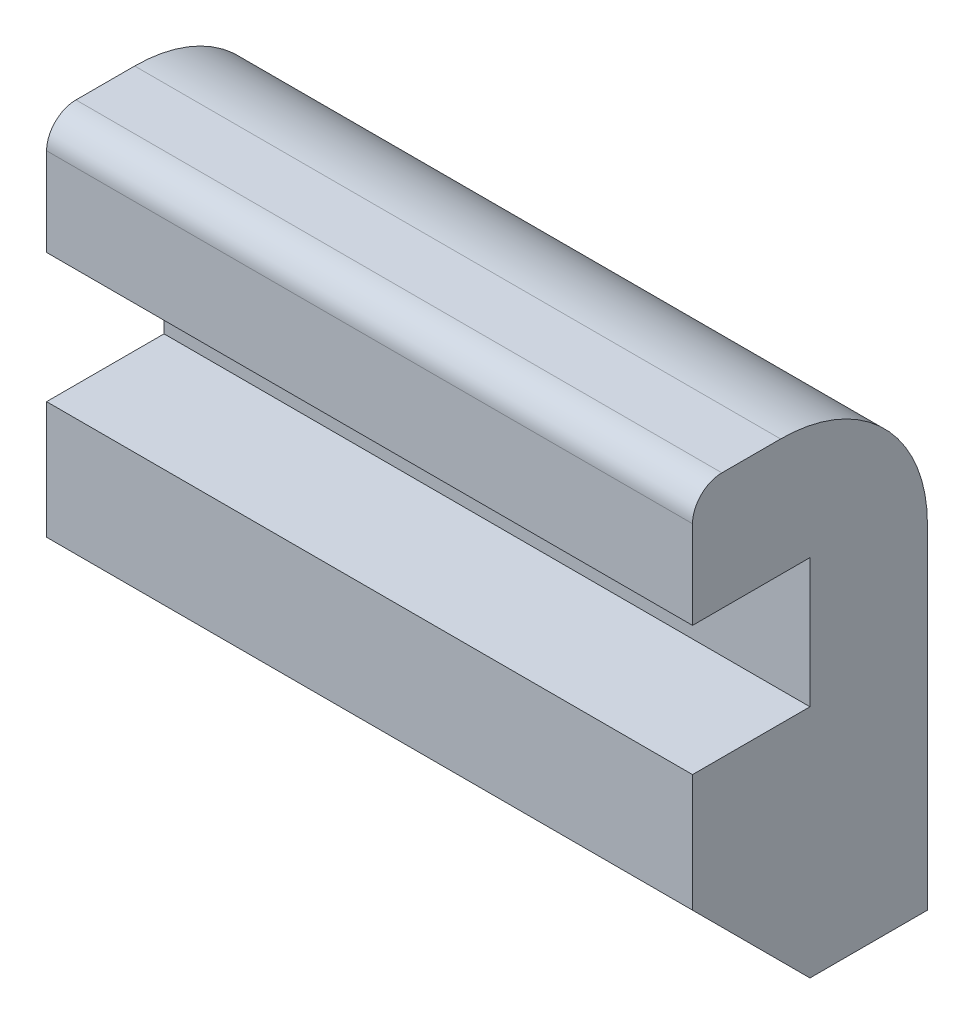
SolidWorks part; units mm, degrees
ref_plane "Front Plane" through (0, 0, 0) normal (0, 0, 1) x (1, 0, 0)
ref_plane "Top Plane" through (0, 0, 0) normal (0, 1, 0) x (1, 0, 0)
ref_plane "Right Plane" through (0, 0, 0) normal (1, 0, 0) x (0, 0, -1)
sketch "Sketch1" plane through (0, 0, 0) normal (0, 1, 0) x (1, 0, 0)
  line L1 (-19.5, 77.5) -> (19.5, 77.5)
  line L2 (-19.5, 77.5) -> (-19.5, -77.5)
  line L3 (-19.5, -77.5) -> (19.5, -77.5)
  line L4 (19.5, 77.5) -> (19.5, -77.5)
  line L5 (-19.5, 77.5) -> (19.5, -77.5) construction
  line L6 (-19.5, -77.5) -> (19.5, 77.5) construction
  point P0 (0, 0)
  dimension "D1" = 39
  dimension "D2" = 155
extrude "Boss-Extrude1" add sketch "Sketch1" along normal blind 2
sketch "Sketch2" plane through (0, 2, 0) normal (0, 1, 0) x (1, 0, 0)
  line L0 (-17.5, -75.5) -> (-17.5, -77.5)
  line L1 (-19.5, 77.5) -> (19.5, 77.5)
  line L2 (-19.5, 77.5) -> (-19.5, -77.5)
  line L3 (-19.5, -77.5) -> (19.5, -77.5)
  line L4 (19.5, 77.5) -> (19.5, -77.5)
  line L5 (-17.5, 75.5) -> (17.5, 75.5)
  line L6 (-17.5, 75.5) -> (-17.5, -75.5)
  line L7 (-17.5, -75.5) -> (17.5, -75.5)
  line L8 (17.5, 75.5) -> (17.5, -75.5)
  line L9 (-17.5, 75.5) -> (17.5, -75.5) construction
  line L10 (-17.5, -75.5) -> (17.5, 75.5) construction
  line L11 (17.5, -75.5) -> (17.5, -77.5)
  point P6 (0, 0)
  line M9 (19.5, -77.5) -> (19.5, 77.5)
  line M10 (19.5, 77.5) -> (-19.5, 77.5)
  line M11 (-19.5, 77.5) -> (-19.5, -77.5)
  line M12 (-19.5, -77.5) -> (19.5, -77.5)
  dimension "D1" = 2
  dimension "D2" = 2
extrude "Boss-Extrude2" add sketch "Sketch2" along normal blind 38 contours L8 L11 L3 L0 L6 L5 M9 M10 M11 M12 region at (-19.0983, 2, 76.5)
sketch "Sketch3" plane through (0, 2, 0) normal (0, 1, 0) x (1, 0, 0)
  line L0 (-17.5, 75.5) -> (-17.5, -77.5) construction
  line L1 (-17.5, -77.5) -> (-15.5, -77.5)
  line L2 (-17.5, -77.5) -> (-17.5, -75.5)
  line L3 (-17.5, -75.5) -> (-15.5, -75.5)
  line L4 (-15.5, -77.5) -> (-15.5, -75.5)
  line L5 (-17.5, -73.3) -> (-15.5, -73.3)
  line L6 (-17.5, -73.3) -> (-17.5, -71.3)
  line L7 (-17.5, -71.3) -> (-15.5, -71.3)
  line L8 (-15.5, -73.3) -> (-15.5, -71.3)
  line L9 (17.5, 75.5) -> (17.5, -77.5) construction
  line L10 (17.5, -77.5) -> (15.5, -77.5)
  line L11 (17.5, -77.5) -> (17.5, -75.5)
  line L12 (17.5, -75.5) -> (15.5, -75.5)
  line L13 (15.5, -77.5) -> (15.5, -75.5)
  line L14 (17.5, -73.3) -> (15.5, -73.3)
  line L15 (17.5, -73.3) -> (17.5, -71.3)
  line L16 (17.5, -71.3) -> (15.5, -71.3)
  line L17 (15.5, -73.3) -> (15.5, -71.3)
  line L18 (15.5, -75.5) -> (15.5, -73.3) construction
  line L19 (-15.5, -73.3) -> (15.5, -73.3) construction
  line L20 (-15.5, -75.5) -> (-15.5, -73.3) construction
  line L21 (-15.5, -75.5) -> (15.5, -75.5) construction
  line L22 (15.5, -71.3) -> (-15.5, -71.3) construction
  dimension "D1" = 2
  dimension "D2" = 2
  dimension "D3" = 2.2
  dimension "D4" = 2
extrude "Boss-Extrude3" add sketch "Sketch3" along normal up to surface (38 mm away) up to face at (0, 40, 0.5)
sketch "Sketch4" plane through (0, 0, -75.5) normal (0, 0, 1) x (1, 0, 0)
  line L0 (-17.5, 40) -> (-15.5, 40)
  line L1 (-17.5, 40) -> (17.5, 40) construction
  line L2 (-15.5, 40) -> (-15.5, 38)
  line L3 (-15.5, 38) -> (-17.5, 38)
  line L5 (-17.5, 38) -> (-17.5, 40)
  line L7 (-17.5, 40) -> (-17.5, 2) construction
  line L8 (-15.5, 33.8) -> (-17.5, 31.8)
  line L9 (-17.5, 31.8) -> (-17.5, 35.8)
  line L10 (-15.5, 33.8) -> (-15.5, 35.8)
  line L11 (-15.5, 35.8) -> (-17.5, 35.8)
  line L12 (0, 0) -> (0, 40) construction
  line L13 (15.5, 35.8) -> (17.5, 35.8)
  line L14 (15.5, 33.8) -> (15.5, 35.8)
  line L15 (17.5, 31.8) -> (17.5, 35.8)
  line L16 (15.5, 33.8) -> (17.5, 31.8)
  line L17 (17.5, 38) -> (17.5, 40)
  line L18 (15.5, 38) -> (17.5, 38)
  line L19 (15.5, 40) -> (15.5, 38)
  line L20 (17.5, 40) -> (15.5, 40)
  dimension "D1" = 2
  dimension "D2" = 2
  dimension "D3" = 45
  dimension "D4" = 2.2
  dimension "D5" = 2
extrude "Boss-Extrude4" add sketch "Sketch4" along normal up to surface (153 mm away) up to face at (0, 20.5, 77.5)
sketch "Sketch5" plane through (0, 2, 0) normal (0, 1, 0) x (1, 0, 0)
  line L1 (-15.5, -77.5) -> (15.5, -77.5)
  line L2 (-15.5, -77.5) -> (-15.5, -75.5)
  line L3 (-15.5, -75.5) -> (15.5, -75.5)
  line L4 (15.5, -77.5) -> (15.5, -75.5)
  line L5 (-15.5, -71.3) -> (15.5, -71.3)
  line L6 (-15.5, -71.3) -> (-15.5, -73.3)
  line L7 (-15.5, -73.3) -> (15.5, -73.3)
  line L8 (15.5, -71.3) -> (15.5, -73.3)
sketch "Sketch6" plane through (0, 0, -75.5) normal (0, 0, 1) x (1, 0, 0)
  line L0 (-17.5, 38) -> (-15.5, 38) construction
  line L1 (-17.5, 38) -> (17.5, 38)
  line L2 (-17.5, 38) -> (-17.5, 35.8)
  line L3 (-17.5, 35.8) -> (17.5, 35.8)
  line L4 (17.5, 38) -> (17.5, 35.8)
  line L5 (-17.5, 38) -> (-17.5, 35.8) construction
  line L6 (-15.5, 35.8) -> (-17.5, 35.8) construction
extrude "Cut-Extrude1" cut sketch "Sketch6" along normal through all
sketch "Sketch7" plane through (0, 2, 0) normal (0, 1, 0) x (1, 0, 0)
  line L1 (-17.5, -75.5) -> (17.5, -75.5)
  line L2 (-17.5, -75.5) -> (-17.5, -73.3)
  line L3 (-17.5, -73.3) -> (17.5, -73.3)
  line L4 (17.5, -75.5) -> (17.5, -73.3)
extrude "Cut-Extrude2" cut sketch "Sketch7" along normal through all
extrude "Boss-Extrude5" add sketch "Sketch5" along normal blind 2
sketch "Sketch8" plane through (0, 0, 0) normal (1, 0, 0) x (0, 0, -1)
  line L0 (75.5, 40) -> (73.5, 40)
  line L1 (-73.3, 40) -> (75.5, 40) construction
  line L2 (73.5, 40) -> (73.5, 38)
  line L3 (-73.3, 38) -> (75.5, 38) construction
  line L4 (73.5, 38) -> (75.5, 38)
  line L5 (75.5, 38) -> (75.5, 40)
  line L6 (75.5, 35.8) -> (73.5, 35.8)
  line L7 (-73.3, 35.8) -> (75.5, 35.8) construction
  line L8 (73.5, 35.8) -> (73.5, 33.8)
  line L9 (-71.3, 33.8) -> (75.5, 33.8) construction
  line L10 (73.5, 33.8) -> (75.5, 31.8)
  line L11 (75.5, 31.8) -> (75.5, 35.8)
  dimension "D1" = 2
extrude "Boss-Extrude6" add sketch "Sketch8" along normal up to surface and the other way up to surface up to face at (17.5, 16.9, -2.1) other way up to face at (-17.5, 16.9, -2.1)
sketch "Sketch10" plane through (-17.5, 0, 0) normal (1, 0, 0) x (0, 0, -1)
  line L1 (-75.5, 35.8) -> (-77.5, 35.8)
  line L2 (-75.5, 35.8) -> (-75.5, 38)
  line L3 (-75.5, 38) -> (-77.5, 38)
  line L4 (-77.5, 35.8) -> (-77.5, 38)
  line L5 (-73.3, 40) -> (-75.5, 40)
  line L6 (-73.3, 40) -> (-73.3, 38)
  line L7 (-73.3, 38) -> (-75.5, 38)
  line L8 (-75.5, 40) -> (-75.5, 38)
  line M1 (-75.5, 40) -> (-75.5, 38)
  line M2 (-75.5, 38) -> (-77.5, 38)
  line M3 (-77.5, 38) -> (-77.5, 35.8)
  line M4 (-77.5, 35.8) -> (-75.5, 35.8)
  line M11 (-73.3, 38) -> (-73.3, 40)
  line M12 (-73.3, 40) -> (-75.5, 40)
extrude "Boss-Extrude8" add sketch "Sketch10" along normal up to surface (2 mm away) contours L2 M4 M2 M3 | L7 M11 M12 M1 region at (-17.5, 39, 74.4) region at (-17.5, 36.9, 76.5) up to face at (-15.5, 39, -0.1)
sketch "Sketch11" plane through (17.5, 0, 0) normal (-1, 0, 0) x (0, 0, 1)
  line L1 (75.5, 35.8) -> (77.5, 35.8)
  line L2 (75.5, 35.8) -> (75.5, 38)
  line L3 (75.5, 38) -> (77.5, 38)
  line L4 (77.5, 35.8) -> (77.5, 38)
  line L5 (73.3, 40) -> (75.5, 40)
  line L6 (73.3, 40) -> (73.3, 38)
  line L7 (73.3, 38) -> (75.5, 38)
  line L8 (75.5, 40) -> (75.5, 38)
  line M2 (75.5, 35.8) -> (77.5, 35.8)
  line M3 (77.5, 35.8) -> (77.5, 38)
  line M4 (77.5, 38) -> (75.5, 38)
  line M5 (75.5, 38) -> (75.5, 40)
  line M6 (75.5, 40) -> (73.3, 40)
  line M7 (73.3, 40) -> (73.3, 38)
extrude "Boss-Extrude9" add sketch "Sketch11" along normal up to surface (2 mm away) contours L2 M2 M3 M4 | L7 M7 M5 M6 region at (17.5, 36.9, 76.5) region at (17.5, 39, 74.4) up to face at (15.5, 39, -0.1)
fillet "Fillet2" radius 2.5 17 edges at (-17.5, 16.9, 71.3) (17.5, 16.9, 71.3) (19.5, 20, 77.5) (-19.5, 20, 77.5) (-19.5, 20, -77.5) (-17.5, 16.9, -75.5) (17.5, 16.9, -75.5) (19.5, 20, -77.5) (-19.5, 40, 0) (0, 40, -77.5) (19.5, 40, 0) (0, 0, -77.5) (0, 0, 77.5) (-19.5, 0, 0) (19.5, 0, 0) (-17.5, 40, 77.5) (17.5, 40, 77.5)
sketch "Sketch13" plane through (0, 0, -77.5) normal (0, 0, -1) x (-1, 0, 0)
  line L0 (15.5, 37.5) -> (15.5, 4) construction
  line L1 (-15.5, 7) -> (15.5, 7)
  line L2 (-15.5, 7) -> (-15.5, 4)
  line L3 (-15.5, 4) -> (15.5, 4)
  line L4 (15.5, 7) -> (15.5, 4)
  dimension "D1" = 3
sketch "Sketch14" plane through (0, 0, -75.5) normal (0, 0, 1) x (1, 0, 0)
  line L1 (-18.25, 9) -> (18.25, 9)
  line L2 (-18.25, 9) -> (-18.25, 1.25)
  line L3 (-18.25, 1.25) -> (18.25, 1.25)
  line L4 (18.25, 9) -> (18.25, 1.25)
  line L5 (15.5, 7) -> (-15.5, 7) construction
  line L7 (17, 0) -> (17, 2.5) construction
  line L8 (19.5, 2.5) -> (17, 2.5) construction
  line L10 (-19.5, 2.5) -> (-17, 2.5) construction
  point P20 (17, 1.25)
  point P23 (18.25, 2.5)
  point P26 (-18.25, 2.5)
  dimension "D1" = 2
extrude "Boss-Extrude10" add sketch "Sketch14" along normal blind 2
extrude "Cut-Extrude4" cut sketch "Sketch13" against normal blind 2
fillet "Fillet3" radius 2 1 edges at (0, 9, -73.5)
fillet "Fillet4" radius 0.5 12 edges at (0, 4, -77.5) (0, 7, -77.5) (15.5, 7, -76.5) (15.5, 4, -76.5) (15.5, 5.5, -77.5) (-15.5, 4, -76.5) (-15.5, 7, -76.5) (-15.5, 5.5, -77.5) (0, 7, -75.5) (-15.5, 5.5, -75.5) (0, 4, -75.5) (15.5, 5.5, -75.5)
sketch "Sketch15" plane through (0, 0, 0) normal (0, -1, 0) x (1, 0, 0)
  line L0 (0, 77.5) -> (0, 0) construction
  line L1 (-17, 77.5) -> (17, 77.5) construction
  line L2 (0, 0) -> (0, -77.5) construction
  line L4 (17, -77.5) -> (-17, -77.5) construction
  circle A0 centre (0, 38.75) radius 5.1
  circle A1 centre (0, -38.75) radius 5.1
  dimension "D1" = 10.2
extrude "Cut-Extrude5" cut sketch "Sketch15" against normal through all
sketch "Sketch16" plane through (0, 2, 0) normal (0, 1, 0) x (1, 0, 0)
  circle A0 centre (0, 38.75) radius 7.1
  circle A1 centre (0, -38.75) radius 7.1
  circle A2 centre (0, 38.75) radius 5.1 construction
  dimension "D1" = 2
extrude "Boss-Extrude11" add sketch "Sketch16" along normal blind 1
fillet "Fillet5" radius 0.5 4 edges at (0, 2, 45.85) (0, 2, -31.65) (0, 3, 45.85) (0, 3, -31.65)
fillet "Fillet7" radius 0.5 8 edges at (15.5, 40, 0.75) (15.5, 39.2678, 76.7678) (-15.5, 40, 0.75) (-15.5, 39.2678, 76.7678) (0, 40, -73.5) (15.5, 20.75, 77.5) (-15.5, 20.75, 77.5) (0, 4, 77.5)
sketch "Sketch17" plane through (0, 0, 0) normal (0, -1, 0) x (1, 0, 0)
  line L0 (-17, -77.5) -> (-17, 70.3)
  line L1 (-17, -77.5) -> (17, -77.5)
  line L2 (17, -77.5) -> (17, 70.3)
  line L3 (17, -75) -> (17, 75) construction
  line L5 (17, 70.3) -> (15, 71.3)
  line L6 (15, 71.3) -> (15, 77.5)
  line L7 (15, 77.5) -> (-15, 77.5)
  line L8 (-15, 77.5) -> (-15, 71.3)
  line L9 (-15, 71.3) -> (-17, 70.3)
  line L10 (-17, 75) -> (-17, -75) construction
  line L12 (-15, 71.3) -> (15, 71.3) construction
  line L13 (17, 70.3) -> (-17, 70.3) construction
  line L14 (0, 71.3) -> (0, 77.5) construction
  line L15 (-17, 77.5) -> (17, 77.5) construction
  arc A0 (-19.5, -75) -> (-17, -77.5) centre (-17, -75) ccw construction
  dimension "D1" = 1
  dimension "D2" = 30
  dimension "D3" = 6.2
extrude "Cut-Extrude6" cut sketch "Sketch17" against normal blind 6
sketch "Sketch18" plane through (0, 0, 0) normal (0, 0, 1) x (1, 0, 0)
  line L0 (15, 9) -> (-15, 9) construction
  line L1 (-14.5, 9) -> (14.5, 9)
  line L2 (-14.5, 9) -> (-14.5, 6)
  line L3 (-14.5, 6) -> (14.5, 6)
  line L4 (14.5, 9) -> (14.5, 6)
  line L5 (-17, 6) -> (17, 6) construction
  line L6 (0, 6) -> (0, 0) construction
  dimension "D1" = 29
extrude "Cut-Extrude8" cut sketch "Sketch18" against normal through all
sketch "Sketch20" plane through (0, 0, 0) normal (0, 0, 1) x (1, 0, 0)
  line L0 (-16, 40) -> (16, 40) construction
  line L1 (-19.5, 40) -> (-14.5, 40)
  line L2 (-19.5, 40) -> (-19.5, 0)
  line L3 (-19.5, 0) -> (-14.5, 0)
  line L4 (-14.5, 40) -> (-14.5, 0)
  line L5 (-14.5, 6) -> (14.5, 6)
  line L6 (-14.5, 6) -> (-14.5, 40)
  line L7 (-14.5, 40) -> (14.5, 40)
  line L8 (14.5, 6) -> (14.5, 40)
  line L9 (14.5, 40) -> (19.5, 40)
  line L10 (14.5, 40) -> (14.5, 0)
  line L11 (14.5, 0) -> (19.5, 0)
  line L12 (19.5, 40) -> (19.5, 0)
  line L13 (-15, 0) -> (-17, 0) construction
  line L14 (-19.5, 2.5) -> (-19.5, 37.5) construction
  line L15 (17, 0) -> (15, 0) construction
  line L16 (19.5, 37.5) -> (19.5, 2.5) construction
extrude "Cut-Extrude11" cut sketch "Sketch20" against normal through all both and the other way through all contours L12 L9 L8 L10 L11 | L1 L2 L3 L4 region at (17, 20, 0)
sketch "Sketch21" plane through (0, 0, 0) normal (0, 0, 1) x (1, 0, 0)
  line L0 (14.5, 40) -> (-14.5, 40) construction
  line L1 (-14.5, 9) -> (14.5, 9)
  line L2 (-14.5, 9) -> (-14.5, 40)
  line L3 (-14.5, 40) -> (14.5, 40)
  line L4 (14.5, 9) -> (14.5, 40)
  line L5 (-14.5, 9) -> (14.5, 40) construction
  line L6 (-14.5, 40) -> (14.5, 9) construction
  line L8 (-5.5, 9) -> (5.5, 9)
  line L9 (-5.5, 9) -> (-5.5, 40)
  line L10 (-5.5, 40) -> (5.5, 40)
  line L11 (5.5, 9) -> (5.5, 40)
  line L12 (-5.5, 9) -> (5.5, 40) construction
  line L13 (-5.5, 40) -> (5.5, 9) construction
  point P0 (0, 24.5)
  point P7 (0, 24.5)
  dimension "D1" = 11
extrude "Cut-Extrude12" cut sketch "Sketch21" against normal through all contours L1 L9 L3 L2 | L11 L1 L4 L3 region at (-10, 24.5, 0) region at (10, 24.5, 0)
sketch "Sketch22" plane through (0, 0, -75.5) normal (0, 0, 1) x (1, 0, 0)
  line L1 (-5.5, 40) -> (5.5, 40)
  line L2 (-5.5, 40) -> (-5.5, 31.8)
  line L3 (-5.5, 31.8) -> (5.5, 31.8)
  line L4 (5.5, 40) -> (5.5, 31.8)
  line L5 (-5.5, 9) -> (5.5, 9)
  line L6 (-5.5, 9) -> (-5.5, 31.8)
  line L7 (-5.5, 31.8) -> (5.5, 31.8)
  line L8 (5.5, 9) -> (5.5, 31.8)
  line M1 (5.5, 31.8) -> (-5.5, 31.8)
  line M2 (-5.5, 31.8) -> (-5.5, 9)
  line M3 (-5.5, 9) -> (5.5, 9)
  line M4 (5.5, 9) -> (5.5, 31.8)
extrude "Cut-Extrude13" cut sketch "Sketch22" against normal through all contours M4 M1 M2 M3 region at (0, 20.4, -75.5)
